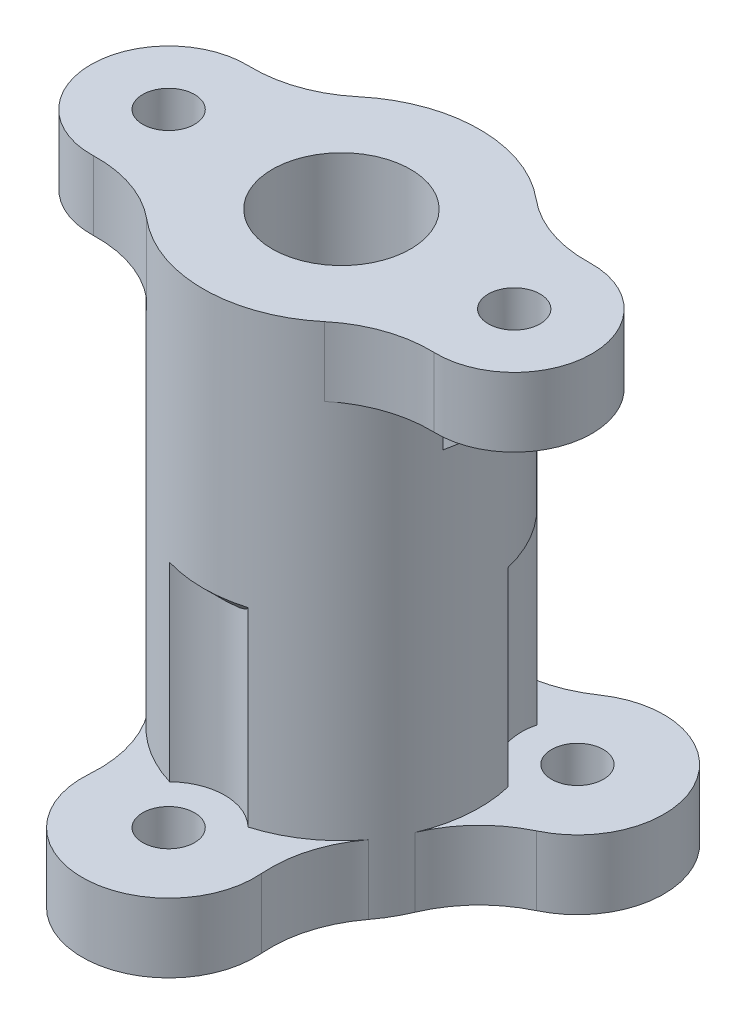
SolidWorks part; units mm, degrees
ref_plane "Спереди" through (0, 0, 0) normal (0, 0, 1) x (1, 0, 0)
ref_plane "Сверху" through (0, 0, 0) normal (0, 1, 0) x (1, 0, 0)
ref_plane "Справа" through (0, 0, 0) normal (1, 0, 0) x (0, 0, -1)
sketch "Sketch1" plane through (0, 0, 0) normal (0, 1, 0) x (1, 0, 0)
  circle A0 centre (0, 0) radius 4
  circle A1 centre (0, 0) radius 8
  dimension "D1" = 8
  dimension "D2" = 4
extrude "Boss-Extrude1" add sketch "Sketch1" along normal blind 30
sketch "Sketch2" plane through (0, 30, 0) normal (0, 1, 0) x (1, 0, 0)
  line L0 (0, 5.7735) -> (0, 0) construction
  circle A0 centre (-10, 0) radius 1.5
  circle A2 centre (-10, 0) radius 4.5
  circle A3 centre (10, 0) radius 4.5
  circle A4 centre (10, 0) radius 1.5
  point P6 (0, 0)
  dimension "D1" = 3
  dimension "D2" = 9
  dimension "D3" = 20
extrude "Boss-Extrude2" add sketch "Sketch2" against normal blind 4
fillet "Fillet1" radius 7 4 edges at (7.1875, 28, 3.5128) (7.1875, 28, -3.5128) (-7.1875, 28, -3.5128) (-7.1875, 28, 3.5128)
sketch "Sketch3" plane through (0, 0, 0) normal (0, -1, 0) x (1, 0, 0)
  circle A0 centre (0, 10) radius 1.5
  circle A1 centre (0, 10) radius 5
  circle A2 centre (8.6603, -5) radius 1.5
  circle A3 centre (8.6603, -5) radius 5
  circle A4 centre (-8.6603, -5) radius 1.5
  circle A5 centre (-8.6603, -5) radius 5
  point P4 (-10.5981, -5.3886)
  point P5 (0, 0)
  point P13 (0, 0)
  dimension "D1" = 3
  dimension "D3" = 10
  dimension "D2" = 10
extrude "Boss-Extrude3" add sketch "Sketch3" against normal blind 4
fillet "Fillet2" radius 7 6 edges at (4.0379, 2, -6.9062) (-4.0379, 2, -6.9062) (-7.9999, 2, -0.0438) (-3.962, 2, 6.95) (7.9999, 2, -0.0438) (3.962, 2, 6.95)
sketch "Sketch4" plane through (0, 4, 0) normal (0, 1, 0) x (1, 0, 0)
  circle A0 centre (8.6603, 5) radius 3.25
  circle A1 centre (0, -10) radius 3.25
  circle A2 centre (-8.6603, 5) radius 3.25
  point P3 (0, 0)
  point P10 (0, 0)
  dimension "D1" = 6.5
extrude "Cut-Extrude1" cut sketch "Sketch4" along normal blind 10
chamfer "Chamfer1" distance 1 angle 45 3 edges at (-6.9282, 14, -4) (0, 14, 8) (6.9282, 14, -4)
sketch "Sketch5" plane through (0, 26, 0) normal (0, -1, 0) x (1, 0, 0)
  line L0 (0, 0) -> (0, 6.0381) construction
  line L1 (-10, 3.1754) -> (-12.75, 1.5877)
  line L2 (-12.75, 1.5877) -> (-12.75, -1.5877)
  line L3 (-12.75, -1.5877) -> (-10, -3.1754)
  line L4 (-10, -3.1754) -> (-7.25, -1.5877)
  line L5 (-7.25, -1.5877) -> (-7.25, 1.5877)
  line L6 (-7.25, 1.5877) -> (-10, 3.1754)
  line L7 (7.25, 1.5877) -> (10, 3.1754)
  line L8 (7.25, -1.5877) -> (7.25, 1.5877)
  line L9 (10, -3.1754) -> (7.25, -1.5877)
  line L10 (12.75, -1.5877) -> (10, -3.1754)
  line L11 (12.75, 1.5877) -> (12.75, -1.5877)
  line L12 (10, 3.1754) -> (12.75, 1.5877)
  circle A0 centre (-10, 0) radius 2.75 construction
  circle A1 centre (10, 0) radius 2.75 construction
  point P20 (-10, 3.1754)
  point P21 (0, 0)
  dimension "D1" = 5.5
extrude "Cut-Extrude2" cut sketch "Sketch5" against normal blind 1.5 and the other way blind 1.5
chamfer "Chamfer2" distance 1 angle 60 1 edges at (-8, 24.5, 0) first distance on face at (-7.5684, 24.5, 0)
chamfer "Chamfer3" distance 1 angle 60 1 edges at (8, 24.5, 0) first distance on face at (7.5684, 24.5, 0)
